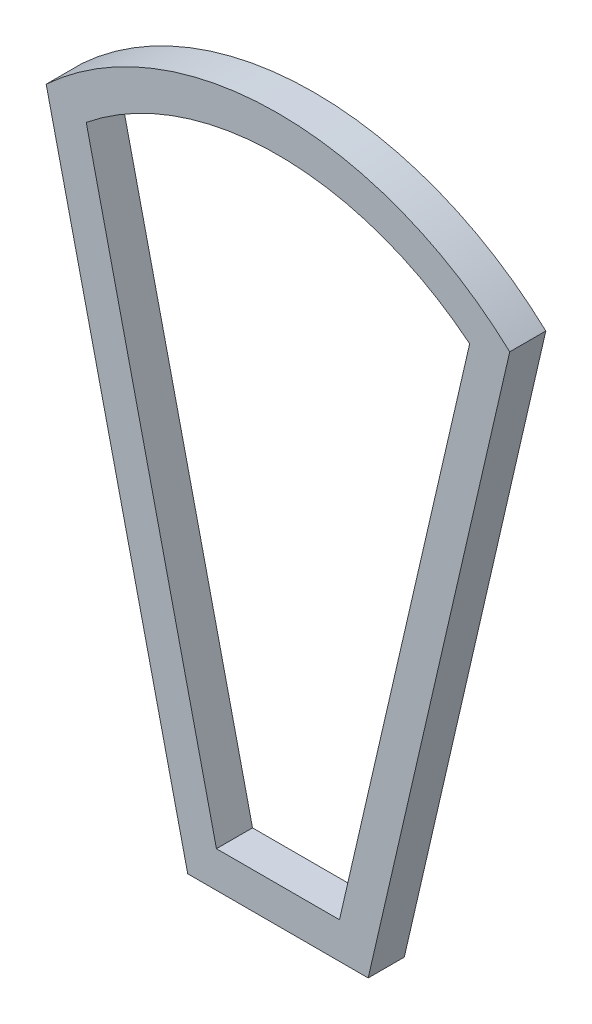
SolidWorks part; units mm, degrees
ref_plane "Front Plane" through (0, 0, 0) normal (0, 0, 1) x (1, 0, 0)
ref_plane "Top Plane" through (0, 0, 0) normal (0, 1, 0) x (1, 0, 0)
ref_plane "Right Plane" through (0, 0, 0) normal (1, 0, 0) x (0, 0, -1)
sketch "Sketch1" plane through (0, 0, 0) normal (0, 0, 1) x (1, 0, 0)
  line L0 (-0.5, -1.7) -> (-1.2843, 1.6971)
  line L1 (-0.5, -1.7) -> (0.5, -1.7)
  line L5 (-0.3409, -1.5) -> (-1.0623, 1.6247)
  line L6 (0.3409, -1.5) -> (1.0623, 1.6247)
  line L7 (0.5, -1.7) -> (1.2843, 1.6971)
  line L8 (-0.3409, -1.5) -> (0.3409, -1.5)
  arc A0 (-1.2843, 1.6971) -> (1.2843, 1.6971) centre (0, 0.3088) cw
  arc A1 (-1.0623, 1.6247) -> (1.0623, 1.6247) centre (0, 0.3088) cw
  point P0 (0, 0)
  point P11 (0, 0)
  dimension "D1" = 0.2
extrude "Boss-Extrude1" add sketch "Sketch1" along normal blind 0.2
